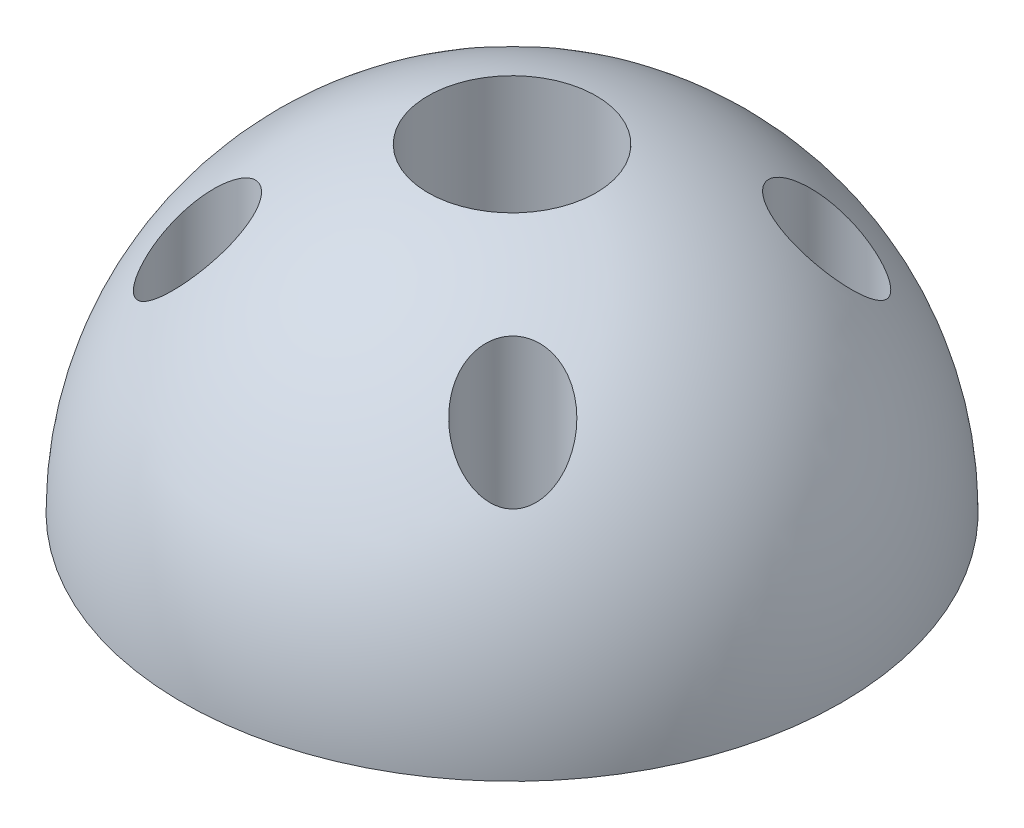
SolidWorks part; units mm, degrees
ref_plane "Front Plane" through (0, 0, 0) normal (0, 0, 1) x (1, 0, 0)
ref_plane "Top Plane" through (0, 0, 0) normal (0, 1, 0) x (1, 0, 0)
ref_plane "Right Plane" through (0, 0, 0) normal (1, 0, 0) x (0, 0, -1)
sketch "Sketch1" plane through (0, 0, 0) normal (0, 0, 1) x (1, 0, 0)
  line L0 (-20, 0) -> (20, 0)
  line L1 (0, -1000) -> (0, 49000) construction
  arc A0 (20, 0) -> (-20, 0) centre (0, 0) ccw
  dimension "D1" = 20
revolve "Revolve1" add sketch "Sketch1" angle 360 about L1 region at (-8.4883, 8.4883, 0)
sketch "Sketch2" plane through (0, 0, 0) normal (0, -1, 0) x (1, 0, 0)
  line L1 (4.8786, -8.45) -> (9.7572, 0)
  line L2 (9.7572, 0) -> (4.8786, 8.45)
  line L3 (4.8786, 8.45) -> (-4.8786, 8.45)
  line L4 (-4.8786, 8.45) -> (-9.7572, 0)
  line L5 (-9.7572, 0) -> (-4.8786, -8.45)
  line L6 (-4.8786, -8.45) -> (4.8786, -8.45)
  circle A0 centre (0, 0) radius 8.45 construction
  dimension "D1" = 16.9
extrude "Cut-Extrude2" cut sketch "Sketch2" against normal blind 3.5
sketch "Sketch3" plane through (0, 3.5, 0) normal (0, -1, 0) x (1, 0, 0)
  line L0 (-4.8786, 8.45) -> (-9.7572, 0) construction
  line L1 (3.7239, -6.45) -> (7.4478, 0)
  line L2 (7.4478, 0) -> (3.7239, 6.45)
  line L3 (3.7239, 6.45) -> (-3.7239, 6.45)
  line L4 (-3.7239, 6.45) -> (-7.4478, 0)
  line L5 (-7.4478, 0) -> (-3.7239, -6.45)
  line L6 (-3.7239, -6.45) -> (3.7239, -6.45)
  circle A0 centre (0, 0) radius 5.1
  circle A1 centre (0, 0) radius 6.45 construction
  dimension "D1" = 10.2
  dimension "D2" = 2
sketch "Sketch7" plane through (0, 0, 0) normal (0, -1, 0) x (1, 0, 0)
  line L0 (707.1068, -707.1068) -> (-34648.2323, 34648.2323) construction
  line L1 (-707.1068, -707.1068) -> (34648.2323, 34648.2323) construction
  circle A0 centre (-9.5459, 9.5459) radius 1.5
  circle A1 centre (9.5243, 9.5243) radius 1.5
  circle A2 centre (9.5027, -9.5459) radius 1.5
  circle A3 centre (-9.5675, -9.5243) radius 1.5
  point P16 (-0.0216, 0)
  dimension "D1" = 3
  dimension "D3" = 13.5
  dimension "D2" = 4
extrude "Cut-Extrude6" cut sketch "Sketch7" against normal blind 7
extrude "Cut-Extrude7" cut sketch "Sketch3" against normal through all contours A0 region at (0, 3.5, 0)
sketch "Sketch8" plane through (0, 0, 0) normal (0, 1, 0) x (1, 0, 0)
  circle A0 centre (-9.5675, 9.5243) radius 2.75
  circle A1 centre (9.5243, 9.5675) radius 2.75
  circle A2 centre (9.5675, -9.5243) radius 2.75
  circle A3 centre (-9.5243, -9.5675) radius 2.75
  point P12 (0, 0)
  dimension "D2" = 5.5
  dimension "D1" = 4
extrude "Cut-Extrude8" cut sketch "Sketch8" along normal through all from offset 4
